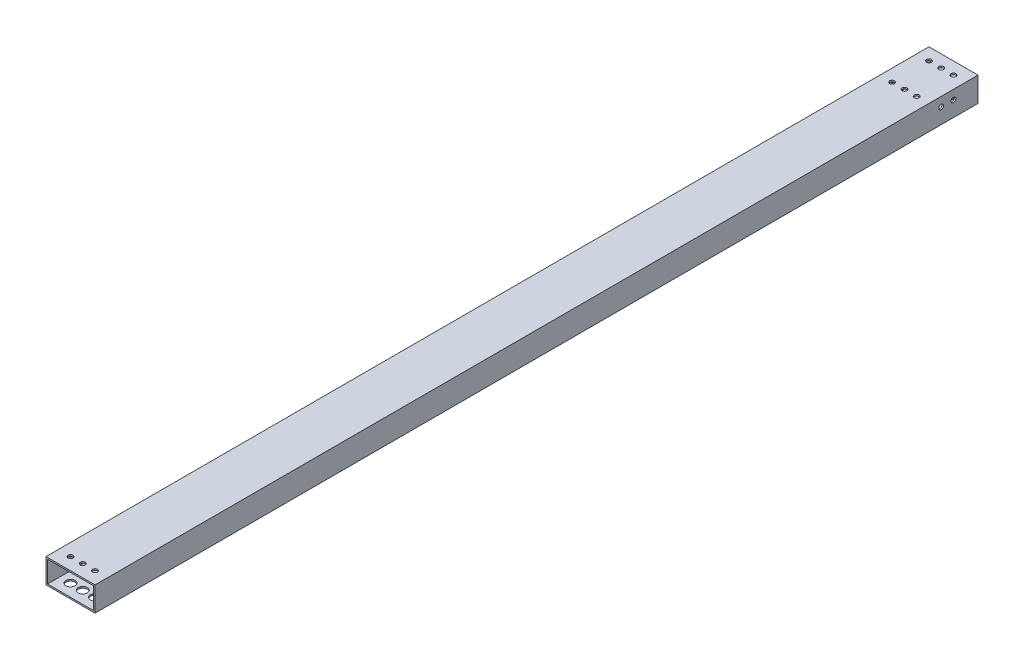
SolidWorks part; units mm, degrees
other "Markup1"
sketch "Sketch5" plane through (-25.4, -12.7, -457.2) normal (-0.35, -0.9329, -0.0852) x (-0.8023, 0.2515, 0.5413)
sketch "Sketch6" plane through (-25.4, -12.7, -457.2) normal (-0.35, -0.9329, -0.0852) x (-0.8023, 0.2515, 0.5413)
sketch "Sketch8" plane through (-25.4, -12.7, -457.2) normal (-0.35, -0.9329, -0.0852) x (-0.8023, 0.2515, 0.5413)
sketch "Sketch9" plane through (-25.4, -12.7, -457.2) normal (-0.35, -0.9329, -0.0852) x (-0.8023, 0.2515, 0.5413)
sketch "Sketch11" plane through (-25.4, -12.7, -457.2) normal (-0.35, -0.9329, -0.0852) x (-0.8023, 0.2515, 0.5413)
sketch "Sketch13" plane through (-25.4, -12.7, -457.2) normal (-0.35, -0.9329, -0.0852) x (-0.8023, 0.2515, 0.5413)
sketch "Sketch14" plane through (-25.4, -12.7, -457.2) normal (-0.35, -0.9329, -0.0852) x (-0.8023, 0.2515, 0.5413)
sketch "Sketch15" plane through (-25.4, -12.7, -457.2) normal (-0.35, -0.9329, -0.0852) x (-0.8023, 0.2515, 0.5413)
material "6061-T6 (SS)"
ref_plane "Front Plane" through (0, 0, 0) normal (0, 0, 1) x (1, 0, 0)
ref_plane "Top Plane" through (0, 0, 0) normal (0, 1, 0) x (1, 0, 0)
ref_plane "Right Plane" through (0, 0, 0) normal (1, 0, 0) x (0, 0, -1)
sketch "Sketch1" plane through (0, 0, 0) normal (0, 0, 1) x (1, 0, 0)
  line L0 (-23.8125, 11.1125) -> (23.8125, 11.1125)
  line L1 (-25.4, -12.7) -> (25.4, -12.7)
  line L2 (-25.4, -12.7) -> (-25.4, 12.7)
  line L3 (-25.4, 12.7) -> (25.4, 12.7)
  line L4 (25.4, -12.7) -> (25.4, 12.7)
  line L5 (-25.4, -12.7) -> (25.4, 12.7) construction
  line L6 (-25.4, 12.7) -> (25.4, -12.7) construction
  line L7 (23.8125, -11.1125) -> (23.8125, 11.1125)
  line L8 (-23.8125, -11.1125) -> (23.8125, -11.1125)
  line L9 (-23.8125, -11.1125) -> (-23.8125, 11.1125)
  point P0 (0, 0)
  dimension "D1" = 50.8
  dimension "D2" = 25.4
  dimension "D3" = 1.5875
extrude "Boss-Extrude1" add sketch "Sketch1" along normal mid plane 914.4
sketch "Sketch3" plane through (0, 12.7, 0) normal (0, 1, 0) x (1, 0, 0)
  line L2 (25.4, -457.2) -> (-25.4, -457.2) construction
  line L3 (25.4, 0) -> (-25.4, 0) construction
  line L4 (25.4, -457.2) -> (25.4, 457.2) construction
  line L5 (-25.4, -457.2) -> (-25.4, 457.2) construction
  circle A0 centre (0, -444.5) radius 2.5527
  circle A1 centre (12.7, -444.5) radius 2.5527
  circle A2 centre (-12.7, -444.5) radius 2.5527
  circle A3 centre (12.7, 444.5) radius 2.5527
  circle A4 centre (0, 444.5) radius 2.5527
  circle A5 centre (-12.7, 444.5) radius 2.5527
  dimension "D1" = 5.1054
  dimension "D2" = 12.7
  dimension "D3" = 12.7
  dimension "D4" = 12.7
extrude "Cut-Extrude2" cut sketch "Sketch3" against normal up to surface (1.5875 mm away) up to face at (0, 11.1125, 0)
sketch "Sketch4" plane through (0, -12.7, 0) normal (0, -1, 0) x (1, 0, 0)
  circle A0 centre (-12.7, 444.5) radius 2.5527 construction
  circle A1 centre (0, 444.5) radius 2.5527 construction
  circle A2 centre (12.7, 444.5) radius 2.5527 construction
  circle A3 centre (-12.7, 444.5) radius 2.5527
  circle A4 centre (0, 444.5) radius 2.5527
  circle A5 centre (12.7, 444.5) radius 2.5527
  circle A6 centre (-12.7, -444.5) radius 2.5527 construction
  circle A7 centre (0, -444.5) radius 2.5527 construction
  circle A8 centre (12.7, -444.5) radius 2.5527 construction
  circle A9 centre (-12.7, -444.5) radius 2.5527
  circle A10 centre (0, -444.5) radius 2.5527
  circle A11 centre (12.7, -444.5) radius 2.5527
  circle A12 centre (-12.7, 444.5) radius 4.7625
  circle A13 centre (0, 444.5) radius 4.7625
  circle A14 centre (12.7, 444.5) radius 4.7625
  circle A15 centre (-12.7, -444.5) radius 4.7625
  circle A16 centre (0, -444.5) radius 4.7625
  circle A17 centre (12.7, -444.5) radius 4.7625
  dimension "D1" = 9.525
  dimension "D2" = 9.525
extrude "Cut-Extrude4" cut sketch "Sketch4" against normal up to surface (1.5875 mm away) contours A12 A3 | A13 A4 | A4 | A3 | A5 | A14 A5 | A11 | A17 A11 | A16 A10 | A10 | A15 A9 | A9 region at (-12.7, -12.7, 444.5) region at (0, -12.7, 444.5) region at (12.7, -12.7, 444.5) region at (-12.7, -12.7, -444.5) region at (0, -12.7, -444.5) region at (12.7, -12.7, -444.5) region at (-17.3278, -12.7, 444.5) region at (-4.6278, -12.7, 444.5) region at (8.0722, -12.7, 444.5) region at (-17.3278, -12.7, -444.5) region at (-4.6278, -12.7, -444.5) region at (8.0722, -12.7, -444.5) up to face at (0, -11.1125, 0)
sketch "Sketch7" plane through (25.4, 0, 0) normal (1, 0, 0) x (0, 0, -1)
  line L1 (-457.2, 12.7) -> (457.2, 12.7) construction
  line L2 (0, 12.7) -> (0, -12.7) construction
  line L3 (-457.2, -12.7) -> (457.2, -12.7) construction
  line L5 (457.2, -12.7) -> (457.2, 12.7) construction
  circle A4 centre (406.4, 3.175) radius 2.4892
  circle A5 centre (419.1, 3.175) radius 2.4892
  circle A6 centre (431.8, 3.175) radius 2.4892
  circle A7 centre (444.5, 3.175) radius 2.4892
  point P2 (0, 0)
  point P3 (433.2987, -2.8101)
  point P6 (0, 0)
  dimension "D3" = 9.525
  dimension "D2" = 4.9784
  dimension "D1" = 12.7
  dimension "D4" = 12.7
  dimension "D5" = 12.7
  dimension "D6" = 12.7
extrude "Cut-Extrude5" cut sketch "Sketch7" against normal through all contours A5 | A6 region at (25.4, 3.175, -419.1) region at (25.4, 3.175, -431.8)
sketch "Sketch10" plane through (0, 12.7, 0) normal (0, 1, 0) x (1, 0, 0)
  line L0 (25.4, 457.2) -> (-25.4, 457.2) construction
  circle A0 centre (-12.7, 406.4) radius 2.5527
  circle A1 centre (0, 406.4) radius 2.5527
  circle A2 centre (12.7, 406.4) radius 2.5527
  dimension "D1" = 5.1054
  dimension "D2" = 12.7
  dimension "D3" = 12.7
  dimension "D4" = 50.8
extrude "Cut-Extrude6" cut sketch "Sketch10" against normal through all
